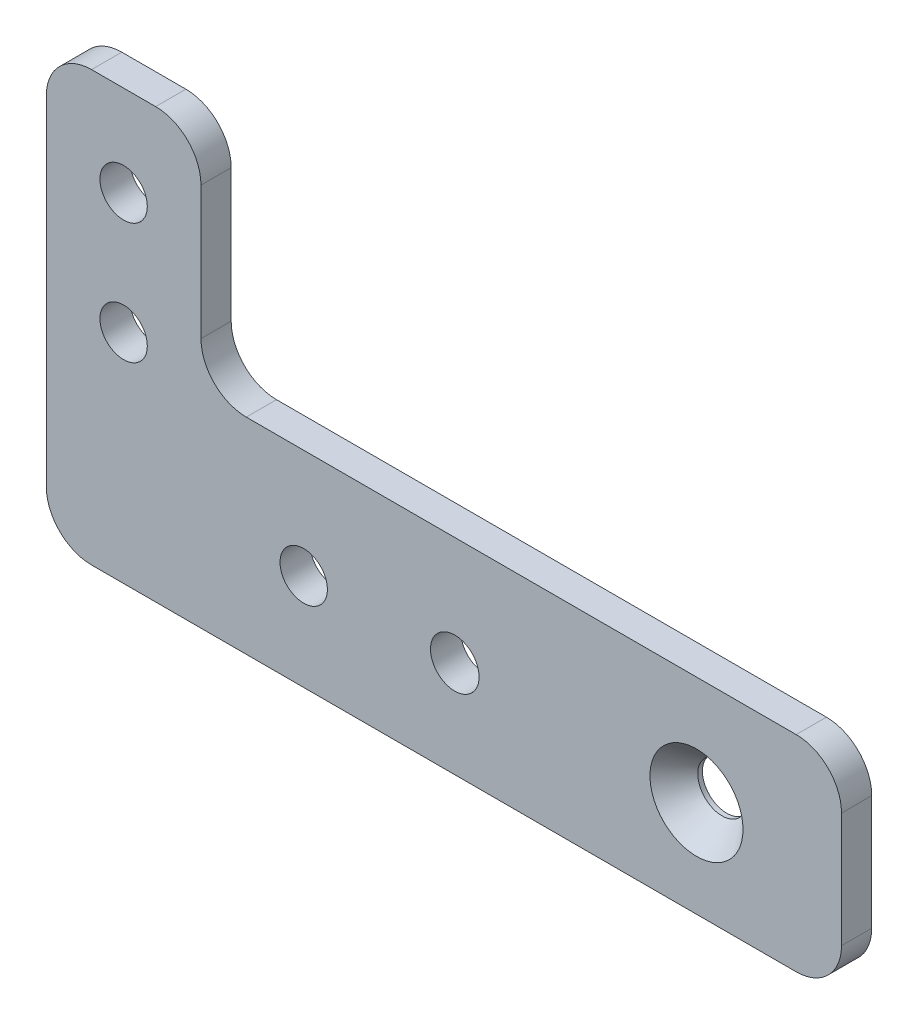
SolidWorks part; units mm, degrees
material "6061-T6 (SS)"
ref_plane "Front Plane" through (0, 0, 0) normal (0, 0, 1) x (1, 0, 0)
ref_plane "Top Plane" through (0, 0, 0) normal (0, 1, 0) x (1, 0, 0)
ref_plane "Right Plane" through (0, 0, 0) normal (1, 0, 0) x (0, 0, -1)
sketch "Sketch1" plane through (0, 0, 0) normal (0, 0, 1) x (1, 0, 0)
  line L0 (-21.59, 23.8125) -> (-37.846, 23.8125) construction
  line L1 (-45.72, -23.8125) -> (45.72, -23.8125)
  line L2 (-45.72, -23.8125) -> (-45.72, 23.8125)
  line L3 (-45.72, 23.8125) -> (45.72, 23.8125)
  line L4 (45.72, -23.8125) -> (45.72, 23.8125)
  line L5 (-45.72, -23.8125) -> (45.72, 23.8125) construction
  line L6 (-45.72, 23.8125) -> (45.72, -23.8125) construction
  line L7 (45.72, 23.8125) -> (-21.59, 23.8125)
  line L8 (45.72, 23.8125) -> (45.72, 0.3175)
  line L9 (45.72, 0.3175) -> (-21.59, 0.3175)
  line L10 (-21.59, 23.8125) -> (-21.59, 0.3175)
  line L11 (-45.72, -23.8125) -> (-37.846, -23.8125)
  line L12 (-45.72, -23.8125) -> (-45.72, 23.8125)
  line L13 (-45.72, 23.8125) -> (-37.846, 23.8125)
  line L14 (-37.846, -23.8125) -> (-37.846, 23.8125)
  line L15 (-37.846, -23.8125) -> (45.72, -23.8125)
  line L16 (-37.846, -23.8125) -> (-37.846, -21.2725)
  line L17 (-37.846, -21.2725) -> (45.72, -21.2725)
  line L18 (45.72, -23.8125) -> (45.72, -21.2725)
  line L19 (-21.59, 23.8125) -> (-37.846, 23.8125) construction
  line L20 (-29.718, 23.8125) -> (-29.718, -21.2725) construction
  circle A0 centre (-29.718, -11.1125) radius 2.4892
  circle A1 centre (-29.718, 1.5875) radius 2.4892
  circle A2 centre (-29.718, 14.2875) radius 2.4892
  circle A4 centre (-10.795, -11.1125) radius 2.4892
  circle A5 centre (5.08, -11.1125) radius 2.5527
  circle A7 centre (30.48, -11.1125) radius 2.5527
  point P0 (0, 0)
  dimension "D7" = 15.24
  dimension "D18" = 5.1054
  dimension "D19" = 4.9784
  dimension "D13" = 25.4
  dimension "D1" = 91.44
  dimension "D2" = 9.525
  dimension "D3" = 24.13
  dimension "D4" = 24.13
  dimension "D5" = 7.874
  dimension "D6" = 47.625
  dimension "D9" = 12.7
  dimension "D10" = 12.7
  dimension "D11" = 12.7
  dimension "D15" = 15.875
  dimension "D16" = 2.54
extrude "Boss-Extrude1" add sketch "Sketch1" along normal blind 3.175 contours L14 L17 L4 L9 L10 L3 A5 A4 A2 A1 A0 | A0 region at (-1.4655, -6.6351, 0) region at (-29.718, -11.1125, 0)
fillet "Fillet1" radius 4.7625 6 edges at (-37.846, 23.8125, 1.5875) (-21.59, 23.8125, 1.5875) (-21.59, 0.3175, 1.5875) (45.72, 0.3175, 1.5875) (45.72, -21.2725, 1.5875) (-37.846, -21.2725, 1.5875)
hole_wizard "CSK for #10 Flat Head Machine Screw1" positions "Sketch3" profile "Sketch4" countersink size "#10" standard "ANSI Inch"
sketch "Sketch3" plane through (0, 0, 3.175) normal (0, 0, 1) x (1, 0, 0)
  point P0 (30.48, -11.1125)
sketch "Sketch4" plane through (30.48, -11.1125, 3.175) normal (1, 0, 0) x (0, -1, 0)
  line L0 (0, 0) -> (0, 20.5838)
  line L1 (0, 20.5838) -> (2.5527, 19.05)
  line L2 (2.5527, 19.05) -> (2.5527, 2.6882)
  line L3 (2.5527, 2.6882) -> (4.8895, 0)
  line L5 (4.8895, 0) -> (0, 0)
  line L6 (-2.5527, 2.6882) -> (-4.8895, 0) construction
  line L10 (0, 20.5838) -> (-2.5527, 19.05) construction
  line L11 (0, -6.35) -> (0, 107.95) construction
  dimension "Hole Dia." = 5.1054
  dimension "Hole Depth" = 19.05
  dimension "Near C'Sink Dia." = 9.779
  dimension "Near C'Sink Angle" = 82
  dimension "Drill Angle" = 118
